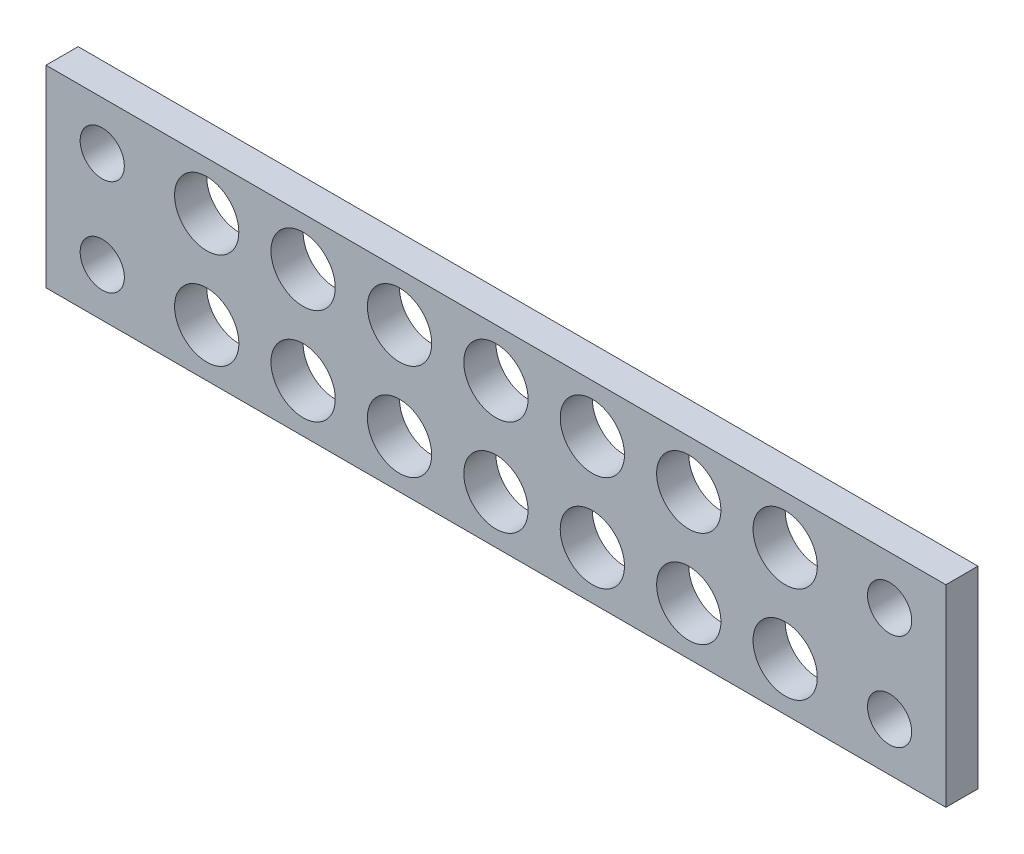
SolidWorks part; units mm, degrees
ref_plane "Front Plane" through (0, 0, 0) normal (0, 0, 1) x (1, 0, 0)
ref_plane "Top Plane" through (0, 0, 0) normal (0, 1, 0) x (1, 0, 0)
ref_plane "Right Plane" through (0, 0, 0) normal (1, 0, 0) x (0, 0, -1)
sketch "Sketch1" plane through (0, 0, 0) normal (0, 0, 1) x (1, 0, 0)
  line L1 (0, 0) -> (42, 0)
  line L2 (0, 0) -> (0, 12)
  line L3 (0, 12) -> (42, 12)
  line L4 (42, 0) -> (42, 12)
  dimension "D1" = 42
  dimension "D2" = 12
extrude "tailLightBase" add sketch "Sketch1" along normal blind 2
sketch "Sketch3" plane through (0, 0, 2) normal (0, 0, 1) x (1, 0, 0)
  line L0 (21, 0) -> (21, 12) construction
  line L1 (0, 12) -> (-7, 12)
  line L2 (0, 12) -> (0, 0)
  line L3 (0, 0) -> (-7, 0)
  line L4 (-7, 12) -> (-7, 0)
  line L5 (0, 0) -> (42, 0) construction
  line L6 (42, 12) -> (0, 12) construction
  line L7 (42, 0) -> (49, 0)
  line L8 (49, 12) -> (49, 0)
  line L9 (42, 12) -> (49, 12)
  line L10 (42, 12) -> (42, 0)
  dimension "D1" = 7
extrude "mountingTabs" add sketch "Sketch3" against normal up to surface (2 mm away) up to face at (21, 6, 0)
sketch "Sketch4" plane through (0, 0, 2) normal (0, 0, 1) x (1, 0, 0)
  line L0 (0, 6) -> (42, 6) construction
  line L3 (21, 0) -> (21, 12) construction
  line L4 (-7, 0) -> (49, 0) construction
  line L5 (0, 6) -> (0, 12) construction
  line L6 (0, 12) -> (0, 0) construction
  line L7 (0, 6) -> (0, 0) construction
  line L8 (42, 0) -> (42, 6) construction
  line L9 (42, 12) -> (42, 0) construction
  line L10 (42, 6) -> (42, 12) construction
  line L11 (0, 6) -> (-7, 6) construction
  line L12 (-7, 12) -> (-7, 0) construction
  line L13 (42, 6) -> (49, 6) construction
  line L14 (49, 12) -> (49, 0) construction
  circle A0 centre (-3.5, 9) radius 1.375
  circle A1 centre (45.5, 9) radius 1.375
  circle A2 centre (-3.5, 3) radius 1.375
  circle A3 centre (45.5, 3) radius 1.375
  point P0 (-3.5, 6)
  point P25 (0, 9)
  dimension "D1" = 2.75
extrude "mountingHoles" cut sketch "Sketch4" against normal blind 2
sketch "Sketch5" plane through (0, 0, 2) normal (0, 0, 1) x (1, 0, 0)
  line L0 (0, 6) -> (42, 6) construction
  circle A0 centre (3, 9) radius 2
  circle A1 centre (9, 9) radius 2
  circle A2 centre (15, 9) radius 2
  circle A3 centre (21, 9) radius 2
  circle A4 centre (27, 9) radius 2
  circle A5 centre (33, 9) radius 2
  circle A6 centre (39, 9) radius 2
  circle A7 centre (39, 3) radius 2
  circle A8 centre (33, 3) radius 2
  circle A9 centre (27, 3) radius 2
  circle A10 centre (21, 3) radius 2
  circle A11 centre (15, 3) radius 2
  circle A12 centre (9, 3) radius 2
  circle A13 centre (3, 3) radius 2
  dimension "D1" = 4
extrude "Cut-Extrude1" cut sketch "Sketch5" against normal blind 10
